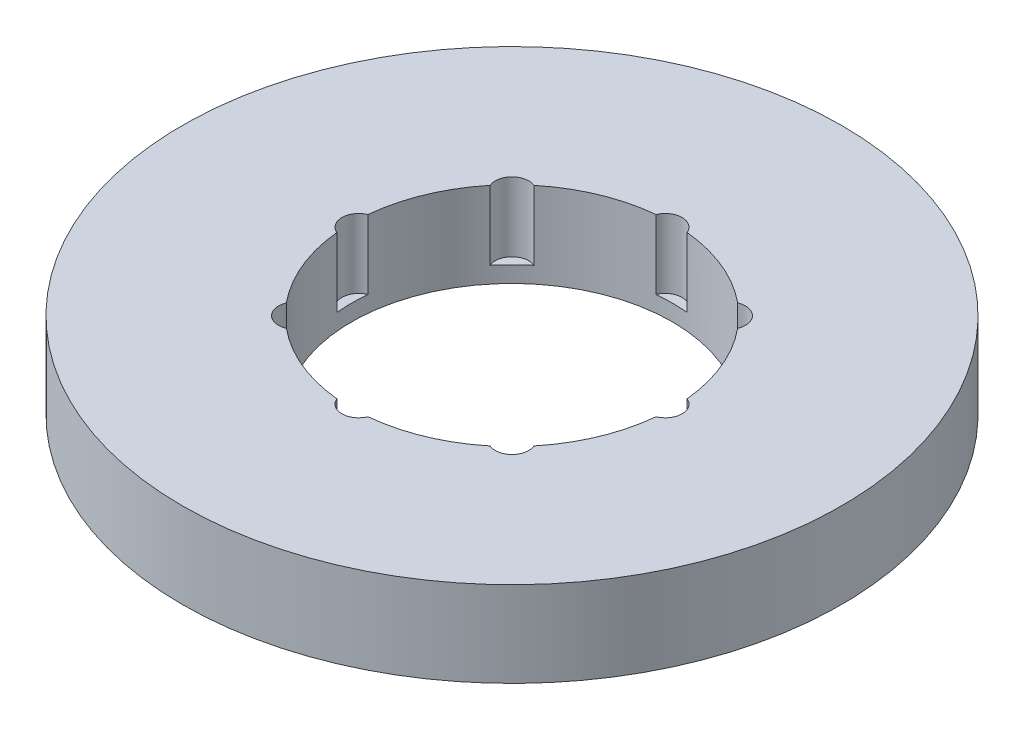
SolidWorks part; units mm, degrees
ref_plane "Front Plane" through (0, 0, 0) normal (0, 0, 1) x (1, 0, 0)
ref_plane "Top Plane" through (0, 0, 0) normal (0, 1, 0) x (1, 0, 0)
ref_plane "Right Plane" through (0, 0, 0) normal (1, 0, 0) x (0, 0, -1)
sketch "Sketch1" plane through (0, 0, 0) normal (0, 1, 0) x (1, 0, 0)
  circle A0 centre (0, 0) radius 92.5
  dimension "FLANGE_OD" = 185
extrude "Boss-Extrude1" add sketch "Sketch1" along normal blind 24
sketch "Sketch2" plane through (0, 0, 0) normal (0, 1, 0) x (1, 0, 0)
  circle A0 centre (0, 0) radius 45
  dimension "BORE_D" = 90
extrude "Cut-Extrude1" cut sketch "Sketch2" along normal through all
sketch "Sketch3" plane through (0, 24, 0) normal (0, 1, 0) x (1, 0, 0)
  circle A0 centre (0, 0) radius 43.0243 construction
  circle A1 centre (-43.0243, 0) radius 4.7077
  dimension "BOLT_D" = 9.4154
  dimension "BOLT_PCD" = 86.0486
extrude "Cut-Extrude2" cut sketch "Sketch3" against normal blind 19.4375
pattern_circular "CirPattern1" count 8 over 360 about axis through (0, 0, 0) along (0, 1, 0) of "Cut-Extrude2"
